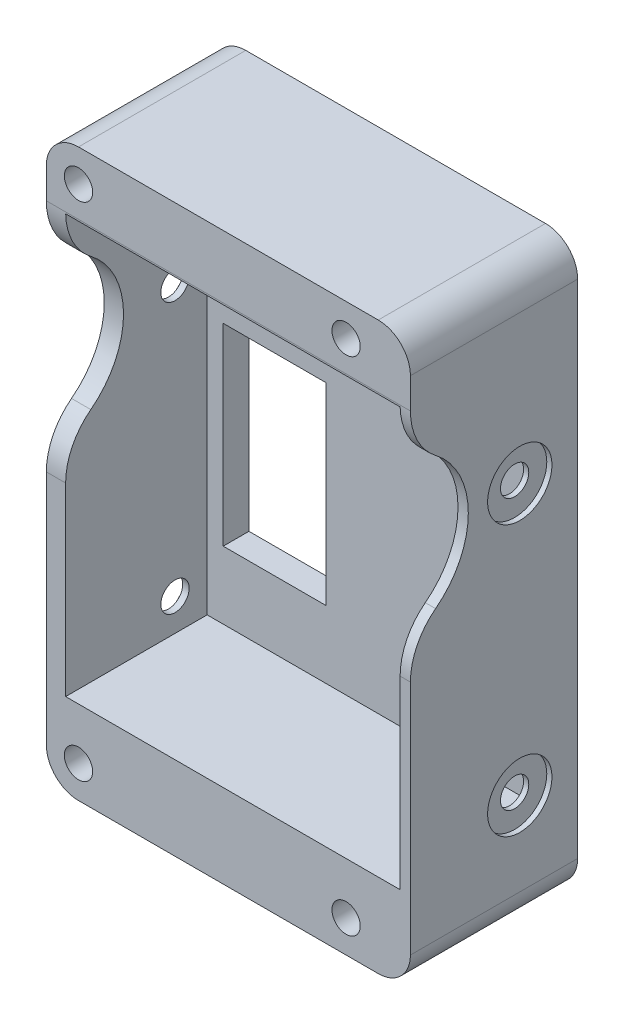
SolidWorks part; units mm, degrees
material "ABS"
ref_plane "正面" through (0, 0, 0) normal (0, 0, 1) x (1, 0, 0)
ref_plane "平面" through (0, 0, 0) normal (0, 1, 0) x (1, 0, 0)
ref_plane "右側面" through (0, 0, 0) normal (1, 0, 0) x (0, 0, -1)
sketch "ｽｹｯﾁ1" plane through (0, 0, 0) normal (0, 0, 1) x (1, 0, 0)
  line L0 (0, 9) -> (26, 9) construction
  line L1 (0, 0) -> (26, 0)
  line L2 (0, 0) -> (0, 32.5)
  line L3 (0, 32.5) -> (26, 32.5)
  line L4 (26, 0) -> (26, 32.5)
  line L5 (26.8, 35) -> (26.8, -4)
  line L6 (24.3, -6.5) -> (1, -6.5)
  line L7 (-1.5, -4) -> (-1.5, 35)
  line L8 (1, 37.5) -> (24.3, 37.5)
  line L9 (26.8, 35) -> (-1.5, 35) construction
  line L10 (1, 37.5) -> (1, -6.5) construction
  line L11 (-1.5, -4) -> (26.8, -4) construction
  circle A0 centre (21.8, 35) radius 1.1
  circle A1 centre (1, 35) radius 1.1
  circle A2 centre (1, -4) radius 1.1
  circle A3 centre (21.8, -4) radius 1.1
  arc A4 (1, -6.5) -> (-1.5, -4) centre (1, -4) cw
  arc A5 (26.8, -4) -> (24.3, -6.5) centre (24.3, -4) cw
  arc A6 (26.8, 35) -> (24.3, 37.5) centre (24.3, 35) ccw
  arc A7 (-1.5, 35) -> (1, 37.5) centre (1, 35) cw
  dimension "D8" = 2.2
  dimension "D9" = 1
  dimension "D14" = 2.5
  dimension "D1" = 32.5
  dimension "D2" = 9
  dimension "D3" = 26
  dimension "D4" = 0.8
  dimension "D5" = 6.5
  dimension "D6" = 1.5
  dimension "D7" = 5
  dimension "D10" = 2.5
  dimension "D11" = 2.5
  dimension "D12" = 5
  dimension "D13" = 5
extrude "ﾎﾞｽ - 押し出し1" add sketch "ｽｹｯﾁ1" along normal blind 11
sketch "ｽｹｯﾁ3" plane through (0, 0, 0) normal (0, 0, -1) x (-1, 0, 0)
  line L4 (1.5, -4) -> (1.5, 35)
  line L5 (-1, 37.5) -> (-24.3, 37.5)
  line L6 (-26.8, 35) -> (-26.8, -4)
  line L7 (-24.3, -6.5) -> (-1, -6.5)
  line L8 (1.5, -4) -> (1.5, 35)
  line L9 (-1, 37.5) -> (-24.3, 37.5)
  line L10 (-26.8, 35) -> (-26.8, -4)
  line L11 (-24.3, -6.5) -> (-1, -6.5)
  circle A0 centre (-21.8, -4) radius 1.1 construction
  circle A1 centre (-1, -4) radius 1.1 construction
  circle A2 centre (-1, 35) radius 1.1 construction
  circle A3 centre (-21.8, 35) radius 1.1 construction
  arc A4 (-1, -6.5) -> (1.5, -4) centre (-1, -4) ccw
  arc A5 (1.5, 35) -> (-1, 37.5) centre (-1, 35) ccw
  arc A6 (-24.3, 37.5) -> (-26.8, 35) centre (-24.3, 35) ccw
  arc A7 (-26.8, -4) -> (-24.3, -6.5) centre (-24.3, -4) ccw
  arc A8 (-1, -6.5) -> (1.5, -4) centre (-1, -4) ccw
  arc A9 (1.5, 35) -> (-1, 37.5) centre (-1, 35) ccw
  arc A10 (-24.3, 37.5) -> (-26.8, 35) centre (-24.3, 35) ccw
  arc A11 (-26.8, -4) -> (-24.3, -6.5) centre (-24.3, -4) ccw
  circle A12 centre (-21.8, -4) radius 1.1
  circle A13 centre (-1, -4) radius 1.1
  circle A14 centre (-1, 35) radius 1.1
  circle A15 centre (-21.8, 35) radius 1.1
  dimension "D1" = 0
extrude "ﾎﾞｽ - 押し出し2" add sketch "ｽｹｯﾁ3" along normal blind 2
sketch "ｽｹｯﾁ2" plane through (-1.5, 0, 0) normal (-1, 0, 0) x (0, 0, 1)
  line L0 (2.5, 43.5506) -> (2.5, -12.0222) construction
  line L1 (0, 32.5) -> (0, 0) construction
  line L2 (11, 32.5) -> (0, 32.5) construction
  circle A0 centre (2.5, 23.5) radius 1.1
  circle A1 centre (2.5, 2.5) radius 1.1
  dimension "D2" = 9
  dimension "D4" = 2.2
  dimension "D1" = 2.5
  dimension "D3" = 21
extrude "ｶｯﾄ - 押し出し1" cut sketch "ｽｹｯﾁ2" against normal through all
sketch "ｽｹｯﾁ4" plane through (0, 0, -2) normal (0, 0, -1) x (-1, 0, 0)
  line L0 (0, 16.25) -> (-26, 16.25) construction
  line L1 (-1.25, 5.25) -> (-9.25, 5.25)
  line L2 (-1.25, 5.25) -> (-1.25, 20.25)
  line L3 (-1.25, 20.25) -> (-9.25, 20.25)
  line L4 (-26, 32.5) -> (-26, 0)
  line L5 (0, 32.5) -> (-26, 32.5)
  line L6 (0, 0) -> (0, 32.5)
  line L7 (-26, 0) -> (0, 0)
  line L8 (-26, 32.5) -> (-26, 0) construction
  line L9 (0, 32.5) -> (-26, 32.5) construction
  line L10 (0, 0) -> (0, 32.5) construction
  line L11 (-26, 0) -> (0, 0) construction
  line L12 (-9.25, 5.25) -> (-9.25, 20.25)
  dimension "D2" = 2.5
  dimension "D3" = 8
  dimension "D4" = 11
  dimension "D5" = 4
  dimension "D1" = 0
extrude "ｶｯﾄ - 押し出し3" cut sketch "ｽｹｯﾁ4" against normal blind 10
sketch "ｽｹｯﾁ5" plane through (26.8, 0, 0) normal (1, 0, 0) x (0, 0, -1)
  line L0 (-11, 32.5) -> (0, 32.5) construction
  line L1 (-11, -4) -> (-11, 35) construction
  circle A0 centre (-13, 23.5) radius 6.5
  dimension "D1" = 9
  dimension "D3" = 13
  dimension "D2" = 2
extrude "ｶｯﾄ - 押し出し4" cut sketch "ｽｹｯﾁ5" against normal through all
fillet "ﾌｨﾚｯﾄ1" radius 5 3 edges at (-0.75, 17.3153, 11) (26.4, 29.6847, 11) (26.4, 17.3153, 11)
sketch "ｽｹｯﾁ6" plane through (26.8, 0, 0) normal (1, 0, 0) x (0, 0, -1)
  circle A0 centre (-2.5, 2.5) radius 2.5
  circle A1 centre (-2.5, 23.5) radius 2.5
  circle A2 centre (-2.5, 23.5) radius 1.1 construction
  dimension "D1" = 5
extrude "ｶｯﾄ - 押し出し5" cut sketch "ｽｹｯﾁ6" against normal blind 0.4
sketch "ｽｹｯﾁ7" plane through (-1.5, 0, 0) normal (-1, 0, 0) x (0, 0, 1)
  circle A0 centre (2.5, 2.5) radius 2.5
  circle A1 centre (2.5, 23.5) radius 2.5
  dimension "D1" = 5
extrude "ｶｯﾄ - 押し出し6" cut sketch "ｽｹｯﾁ7" against normal blind 1
